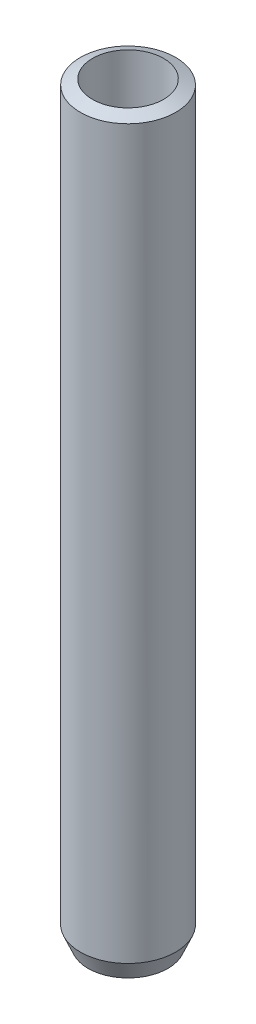
SolidWorks part; units mm, degrees
ref_plane "Front Plane" through (0, 0, 0) normal (0, 0, 1) x (1, 0, 0)
ref_plane "Top Plane" through (0, 0, 0) normal (0, 1, 0) x (1, 0, 0)
ref_plane "Right Plane" through (0, 0, 0) normal (1, 0, 0) x (0, 0, -1)
sketch "Sketch1" plane through (0, 0, 0) normal (0, 1, 0) x (1, 0, 0)
  circle A0 centre (0, 0) radius 30
  dimension "SHAFT_OD" = 60
extrude "Boss-Extrude1" add sketch "Sketch1" along normal blind 473.8734
sketch "Sketch2" plane through (0, 0, 0) normal (0, 1, 0) x (1, 0, 0)
  circle A0 centre (0, 0) radius 22.3832
  dimension "BORE_D" = 44.7664
extrude "Cut-Extrude1" cut sketch "Sketch2" along normal through all
chamfer "Chamfer1" distance 4.8739 angle 66.775 2 edges at (0, 473.8734, 30) (0, 0, 30) first distance on face at (0, 473.8734, 30) first distance on face at (0, 0, 22.3832)
